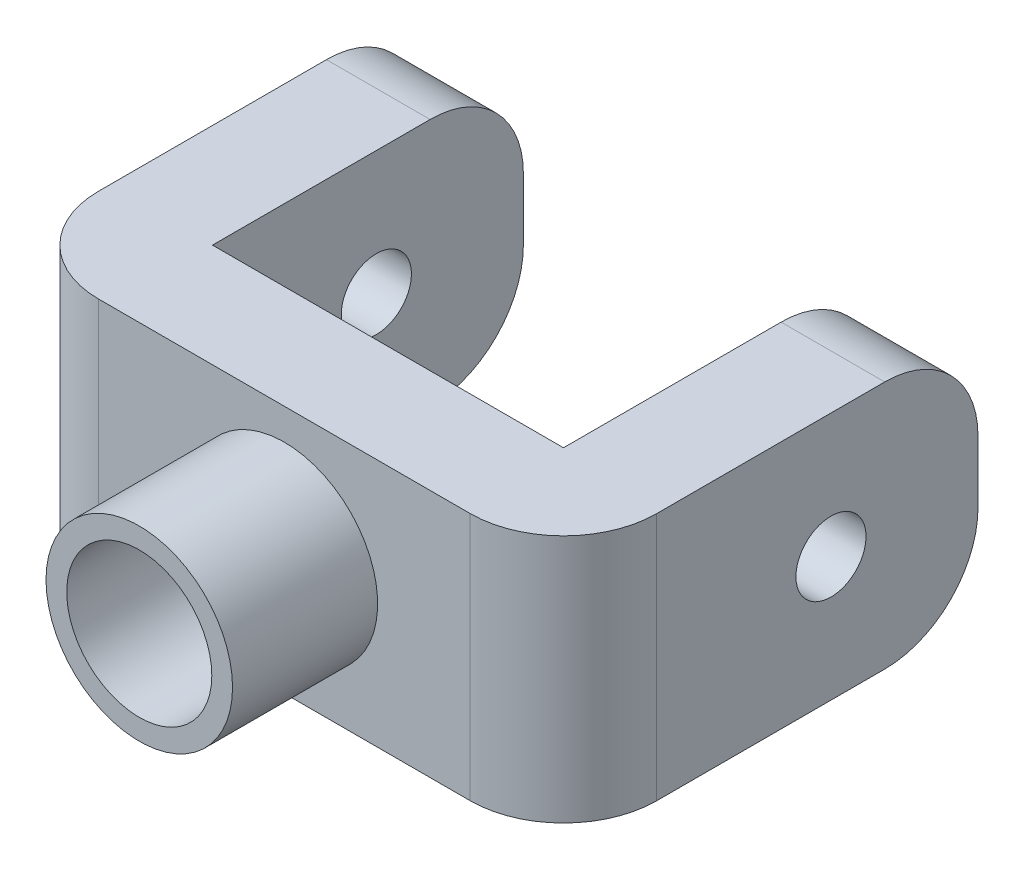
SolidWorks part; units mm, degrees
ref_plane "Front Plane" through (0, 0, 0) normal (0, 0, 1) x (1, 0, 0)
ref_plane "Top Plane" through (0, 0, 0) normal (0, 1, 0) x (1, 0, 0)
ref_plane "Right Plane" through (0, 0, 0) normal (1, 0, 0) x (0, 0, -1)
sketch "Sketch1" plane through (0, 0, 0) normal (0, 1, 0) x (1, 0, 0)
  line L0 (-16.9355, 6.9485) -> (16.9355, 6.9485)
  line L1 (16.9355, 6.9485) -> (16.9355, 36.9485)
  line L2 (16.9355, 36.9485) -> (26.9355, 36.9485)
  line L3 (26.9355, 36.9485) -> (26.9355, -3.0515)
  line L4 (26.9355, -3.0515) -> (-26.9355, -3.0515)
  line L6 (-26.9355, 36.9485) -> (-26.9355, -3.0515)
  line L7 (-16.9355, 36.9485) -> (-26.9355, 36.9485)
  line L8 (-16.9355, 6.9485) -> (-16.9355, 36.9485)
  point P0 (-21.9355, 36.9485)
  dimension "D1" = 10
  dimension "D2" = 40
  dimension "D3" = 10
  dimension "D4" = 40
extrude "Boss-Extrude1" add sketch "Sketch1" along normal mid plane 24
sketch "Sketch2" plane through (0, 0, 3.0515) normal (0, 0, 1) x (1, 0, 0)
  circle A0 centre (0, 0) radius 7
  circle A1 centre (0, 0) radius 9
  dimension "D1" = 18
  dimension "D2" = 14
extrude "Cut-Extrude1" cut sketch "Sketch2" against normal mid plane 34 contours A0
extrude "Boss-Extrude2" add sketch "Sketch2<3>" along normal blind 14
sketch "Sketch2<3>" plane through (0, 0, 3.0515) normal (0, 0, 1) x (1, 0, 0) same geometry as "Sketch2"
sketch "Sketch5" plane through (26.9355, 0, 0) normal (1, 0, 0) x (0, 0, -1)
  circle A0 centre (22.7618, 0) radius 3.3824
extrude "Cut-Extrude2" cut sketch "Sketch5" against normal blind 69 and the other way blind 16
fillet "Fillet2" radius 9 4 edges at (-21.9355, 12, -36.9485) (-21.9355, -12, -36.9485) (21.9355, -12, -36.9485) (21.9355, 12, -36.9485)
fillet "Fillet3" radius 9 2 edges at (-26.9355, 0, 3.0515) (26.9355, 0, 3.0515)
